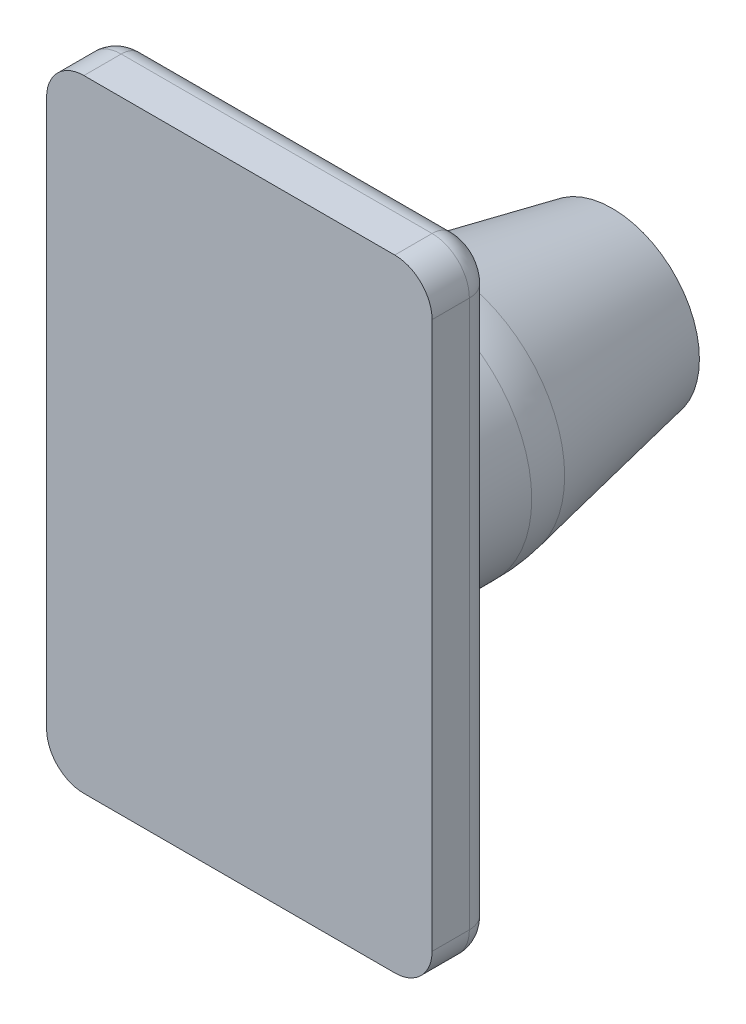
SolidWorks part; units mm, degrees
ref_plane "Front Plane" through (0, 0, 0) normal (0, 0, 1) x (1, 0, 0)
ref_plane "Top Plane" through (0, 0, 0) normal (0, 1, 0) x (1, 0, 0)
ref_plane "Right Plane" through (0, 0, 0) normal (1, 0, 0) x (0, 0, -1)
sketch "Sketch1" plane through (0, 0, 0) normal (0, 0, 1) x (1, 0, 0)
  line L1 (-95.5, -33) -> (-64.5, -33)
  line L2 (-95.5, -33) -> (-95.5, -83)
  line L3 (-95.5, -83) -> (-64.5, -83)
  line L4 (-64.5, -33) -> (-64.5, -83)
extrude "Boss-Extrude1" add sketch "Sketch1" along normal blind 5
fillet "Fillet1" radius 3 4 edges at (-64.5, -83, 2.5) (-64.5, -33, 2.5) (-95.5, -83, 2.5) (-95.5, -33, 2.5)
sketch "Sketch3" plane through (0, 0, 0) normal (0, 0, -1) x (-1, 0, 0)
  circle A0 centre (80, -58) radius 6.55
  circle A1 centre (80, -58) radius 10
extrude "Boss-Extrude2" add sketch "Sketch3" along normal blind 25
chamfer "Chamfer2" distance 15 distance2 3 1 edges at (-90, -58, -25) first distance on face at (-90, -58, -25)
fillet "Fillet2" radius 15 1 edges at (-90, -58, -10)
fillet "Fillet3" radius 2 8 edges at (-94.6213, -33.8787, 0) (-80, -33, 0) (-65.3787, -33.8787, 0) (-64.5, -58, 0) (-65.3787, -82.1213, 0) (-80, -83, 0) (-94.6213, -82.1213, 0) (-95.5, -58, 0)
